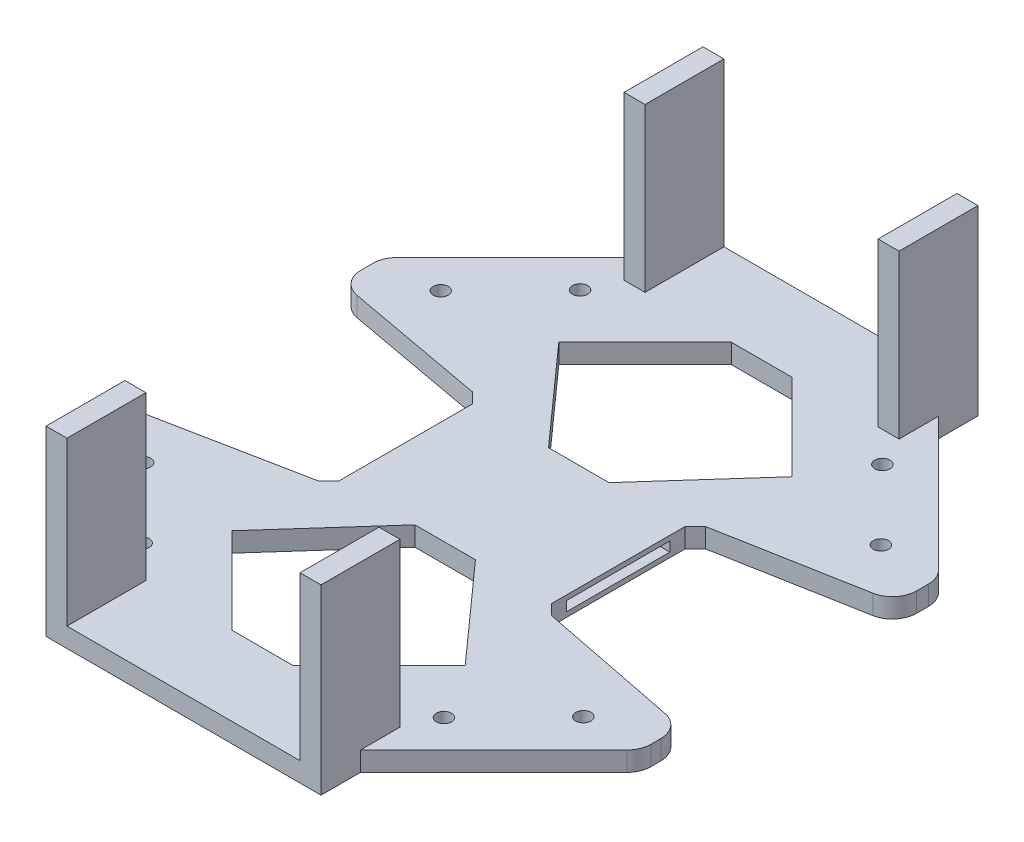
SolidWorks part; units mm, degrees
ref_plane "Front Plane" through (0, 0, 0) normal (0, 0, 1) x (1, 0, 0)
ref_plane "Top Plane" through (0, 0, 0) normal (0, 1, 0) x (1, 0, 0)
ref_plane "Right Plane" through (0, 0, 0) normal (1, 0, 0) x (0, 0, -1)
sketch "Sketch1" plane through (0, 0, 0) normal (0, 1, 0) x (1, 0, 0)
  line L0 (9.3853, 59.817) -> (7.239, 61.9633)
  line L33 (7.239, 114.554) -> (2.8509, 114.554)
  line L34 (7.239, 114.554) -> (7.239, 98.044)
  line L35 (7.239, 98.044) -> (2.8509, 98.044)
  line L36 (2.8509, 114.554) -> (2.8509, 98.044)
  line L37 (7.239, 61.9633) -> (7.239, 98.044)
  line L38 (55.9816, 98.044) -> (60.3697, 98.044)
  line L39 (60.3697, 114.554) -> (60.3697, 98.044)
  line L40 (55.9816, 114.554) -> (60.3697, 114.554)
  line L41 (55.9816, 114.554) -> (55.9816, 98.044)
  line L42 (55.9816, -22.86) -> (55.9816, -6.35)
  line L43 (55.9816, -22.86) -> (60.3697, -22.86)
  line L44 (60.3697, -22.86) -> (60.3697, -6.35)
  line L45 (55.9816, -6.35) -> (60.3697, -6.35)
  line L46 (7.239, -6.35) -> (2.8509, -6.35)
  line L47 (2.8509, -22.86) -> (2.8509, -6.35)
  line L48 (7.239, -22.86) -> (2.8509, -22.86)
  line L49 (7.239, -22.86) -> (7.239, -6.35)
  line L50 (-26.4861, 76.962) -> (2.8509, 106.299)
  line L51 (2.8509, -14.605) -> (-26.4861, 14.732)
  line L52 (-26.4861, 14.732) -> (-26.4861, 76.962)
  line L53 (7.239, 61.9633) -> (-26.4861, 68.1505)
  line L54 (7.239, 29.7307) -> (-26.4861, 23.0392)
  line L55 (60.3697, -14.605) -> (89.7067, 14.732)
  line L56 (9.3853, 31.877) -> (7.239, 29.7307)
  line L57 (9.3853, 59.817) -> (53.8353, 59.817)
  line L58 (9.3853, 59.817) -> (9.3853, 31.877)
  line L59 (9.3853, 31.877) -> (53.8353, 31.877)
  line L60 (53.8353, 59.817) -> (53.8353, 31.877)
  line L61 (7.239, 29.7307) -> (7.239, -6.35)
  line L62 (55.9816, 29.7307) -> (89.7067, 23.0392)
  line L63 (55.9816, 29.7307) -> (55.9816, -6.35)
  line L64 (53.8353, 31.877) -> (55.9816, 29.7307)
  line L65 (53.8353, 59.817) -> (55.9816, 61.9633)
  line L66 (55.9816, 61.9633) -> (55.9816, 98.044)
  line L67 (7.239, 11.6903) -> (25.2794, -6.35)
  line L68 (7.239, 114.554) -> (55.9816, 114.554)
  line L69 (7.239, 114.554) -> (7.239, 98.044)
  line L70 (7.239, 98.044) -> (55.9816, 98.044)
  line L71 (55.9816, 114.554) -> (55.9816, 98.044)
  line L72 (7.239, -6.35) -> (55.9816, -6.35)
  line L73 (7.239, -6.35) -> (7.239, -22.86)
  line L74 (7.239, -22.86) -> (55.9816, -22.86)
  line L75 (55.9816, -6.35) -> (55.9816, -22.86)
  line L76 (55.9816, 11.6903) -> (37.9412, -6.35)
  line L77 (55.9816, 61.9633) -> (89.7067, 68.1505)
  line L78 (7.239, 80.0037) -> (25.2794, 98.044)
  line L79 (55.9816, 80.0037) -> (37.9412, 98.044)
  line L80 (89.7067, 14.732) -> (89.7067, 76.962)
  line L81 (89.7067, 76.962) -> (60.3697, 106.299)
  line L82 (7.239, 80.0037) -> (25.2794, 59.817)
  line L83 (55.9816, 80.0037) -> (37.9412, 59.817)
  line L84 (7.239, 11.6903) -> (25.2794, 31.877)
  line L85 (55.9816, 11.6903) -> (37.9412, 31.877)
  line L86 (31.6103, 114.554) -> (31.6103, 103.0092)
  circle A6 centre (0, 91.694) radius 1.5875
  circle A7 centre (-14.4272, 76.962) radius 1.5875
  circle A8 centre (-14.4272, 14.732) radius 1.5875
  circle A9 centre (0, 0) radius 1.5875
  circle A10 centre (63.2206, 0) radius 1.5875
  circle A11 centre (77.6478, 14.732) radius 1.5875
  circle A12 centre (77.6478, 76.962) radius 1.5875
  circle A13 centre (63.2206, 91.694) radius 1.5875
  dimension "D5" = 44.45
  dimension "D6" = 27.94
extrude "Boss-Extrude2" add sketch "Sketch1" along normal blind 4.064 contours L53 L37 L35 L36 L50 L52 A7 A6 | L61 L54 L52 L51 L47 L46 A9 A8 | L55 L80 L62 L63 L45 L44 A11 A10 | L80 L81 L39 L38 L66 L77 A13 A12 | L34 L70 L41 L68 | L40 L41 L38 L39 | L33 L36 L35 L34 | L48 L49 L46 L47 | L49 L74 L42 L72 | L45 L42 L43 L44 | L63 L76 L72 | L85 L63 L64 L59 | L61 L84 L59 L56 | L61 L72 L67 | L60 L57 L58 L59 | L82 L37 L0 L57 | L37 L78 L70 | L79 L66 L70 | L66 L83 L57 L65 region at (13.3203, 0, -66.6229) region at (31.6103, 0, -45.847) region at (-6.2497, 0, -79.8491) region at (13.3203, 0, -25.0711) region at (13.2525, 0, -92.0306) region at (49.9003, 0, -66.6229) region at (-6.1647, 0, -11.7165) region at (5.0449, 0, -106.299) region at (7.7536, 0, -106.299) region at (69.4703, 0, -79.8491) region at (49.9681, 0, -92.0306) region at (13.2525, 0, 0.3365) region at (49.9003, 0, -25.0711) region at (58.1757, 0, -106.299) region at (5.0449, 0, 14.605) region at (31.6103, 0, 14.605) region at (69.3853, 0, -11.7165) region at (49.9681, 0, 0.3366) region at (58.1757, 0, 14.605)
sketch "Sketch3" plane through (9.3853, 0, 0) normal (-1, 0, 0) x (0, 0, 1)
  line L1 (-59.817, 4.064) -> (-31.877, 4.064)
  line L2 (-59.817, 4.064) -> (-59.817, 0)
  line L3 (-59.817, 0) -> (-31.877, 0)
  line L4 (-31.877, 4.064) -> (-31.877, 0)
  line L5 (-56.642, 3.048) -> (-35.052, 3.048)
  line L6 (-56.642, 3.048) -> (-56.642, 1.016)
  line L7 (-56.642, 1.016) -> (-35.052, 1.016)
  line L8 (-35.052, 3.048) -> (-35.052, 1.016)
  point P10 (-35.052, 2.032)
  point P11 (-31.877, 2.032)
  point P12 (-45.847, 3.048)
  point P13 (-45.847, 4.064)
  dimension "D1" = 2.032
  dimension "D2" = 21.59
extrude "Cut-Extrude1" cut sketch "Sketch3" against normal through all contours L8 L5 L6 L7 region at (9.3853, 2.032, -45.847)
extrude "Boss-Extrude3" add sketch "Sketch1<7>" along normal blind 38.1 contours L33 L36 L35 L34 | L40 L41 L38 L39 | L45 L42 L43 L44 | L48 L49 L46 L47 region at (5.0449, 0, -106.299) region at (58.1757, 0, -106.299) region at (5.0449, 0, 14.605) region at (58.1757, 0, 14.605)
sketch "Sketch1<7>" plane through (0, 0, 0) normal (0, 1, 0) x (1, 0, 0) same geometry as "Sketch1"
fillet "Fillet1" radius 5.08 1 edges at (-26.4861, 2.032, -76.962)
fillet "Fillet2" radius 5.08 1 edges at (-26.4861, 2.032, -68.1505)
fillet "Fillet3" radius 5.08 6 edges at (89.7067, 2.032, -68.1505) (89.7067, 2.032, -76.962) (89.7067, 2.032, -14.732) (89.7067, 2.032, -23.0392) (-26.4861, 2.032, -14.732) (-26.4861, 2.032, -23.0392)
